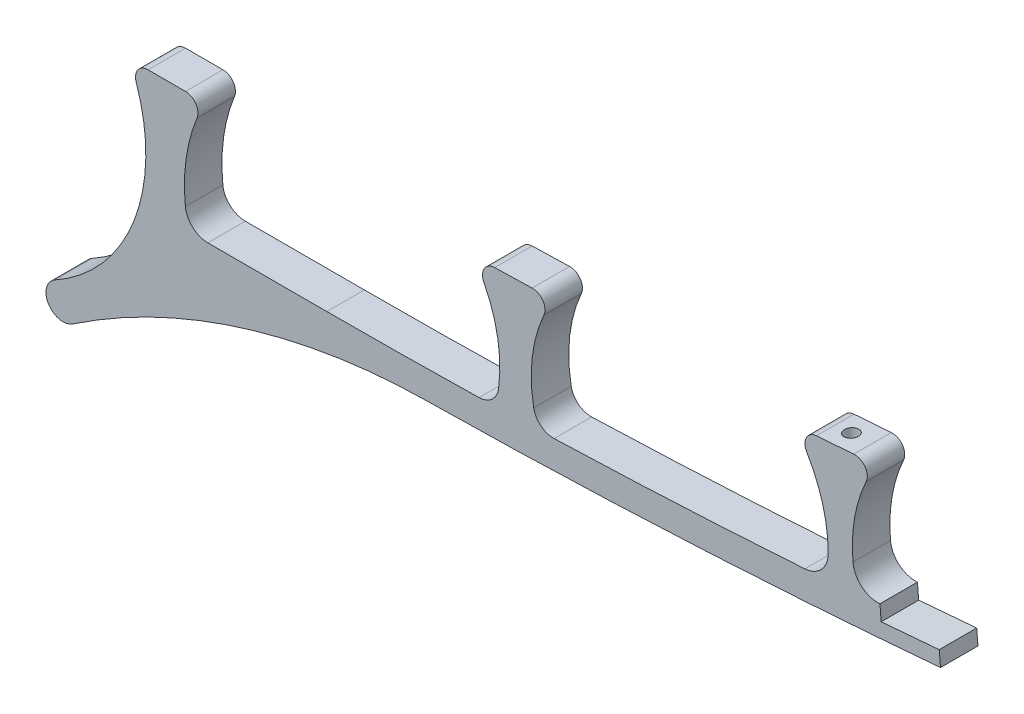
SolidWorks part; units mm, degrees
ref_plane "Front Plane" through (0, 0, 0) normal (0, 0, 1) x (1, 0, 0)
ref_plane "Top Plane" through (0, 0, 0) normal (0, 1, 0) x (1, 0, 0)
ref_plane "Right Plane" through (0, 0, 0) normal (1, 0, 0) x (0, 0, -1)
sketch "Sketch1" plane through (0, 0, 4.0971) normal (0, 0, -1) x (-1, 0, 0)
  line L0 (-62.7619, -51.7222) -> (-58.001, -51.5972) construction
  line L1 (-62.7619, -51.7222) -> (-58.001, -51.5972)
  line L2 (-250.1152, -63.0874) -> (-250.684, -56.8905) construction
  line L3 (-250.1152, -63.0874) -> (-250.684, -56.8905)
  line L4 (5.0134, -50.6875) -> (4.8506, -13.0704)
  line L5 (293.8258, -32.3629) -> (292.5411, -55.9947)
  line L6 (459.2981, -30.7507) -> (468.8231, -30.7507)
  line L7 (423.3798, -61.2307) -> (453.91, -61.2307)
  line L10 (423.2417, -37.1007) -> (607.4086, -37.1007) construction
  line L11 (270.0646, -24.076) -> (423.3798, -30.7507) construction
  line L12 (269.6518, -30.414) -> (423.1036, -37.0947) construction
  line L13 (270.0646, -24.076) -> (423.3798, -30.7507) construction
  line L14 (269.6518, -30.414) -> (423.2417, -37.1007) construction
  line L15 (270.0646, -24.076) -> (423.3798, -30.7507) construction
  line L16 (268.1133, -54.0366) -> (422.0742, -60.7394) construction
  line L17 (268.1133, -54.0366) -> (282.8559, -55.2703)
  line L39 (464.0606, -30.7507) -> (464.0606, -61.2307)
  line L43 (423.3798, -61.2307) -> (607.4086, -61.2307) construction
  line L44 (375.9837, -30.118) -> (375.1663, -60.587)
  line L45 (423.3798, -30.7507) -> (607.4086, -30.7507) construction
  arc A10 (295.9963, -50.7756) -> (301.9161, -57.1188) centre (302.3463, -50.7834) ccw
  arc A11 (301.4662, -31.1688) -> (298.9719, -26.3615) centre (298.7477, -29.5285) ccw
  arc A12 (289.4896, -25.6646) -> (286.3657, -30.1613) centre (289.2483, -28.8304) ccw
  arc A13 (282.8559, -55.2703) -> (289.7096, -49.5155) centre (283.3855, -48.9424) ccw
  arc A17 (301.4662, -31.1688) -> (295.9963, -50.7756) centre (334.0387, -50.8222) ccw
  arc A18 (289.7096, -49.5155) -> (286.3657, -30.1613) centre (251.8722, -46.0867) ccw
  circle A19 centre (490.3927, -92.6507) radius 4.3495
  arc A24 (383.4811, -34.8689) -> (379.749, -56.3925) centre (415.8403, -51.5652) ccw
  circle A29 centre (384.8064, -55.7161) radius 5.1024
  arc A30 (471.8244, -34.9614) -> (468.8231, -30.7507) centre (468.8231, -33.9257) ccw
  arc A31 (459.2981, -30.7507) -> (456.3562, -35.1198) centre (459.2981, -33.9257) ccw
  circle A32 centre (453.6208, -55.4881) radius 5.7427
  arc A33 (383.4811, -34.8689) -> (380.7361, -30.239) centre (380.6595, -33.4131) ccw
  arc A36 (459.3328, -56.0812) -> (456.3562, -35.1198) centre (415.8403, -51.5652) ccw
  arc A39 (368.2424, -34.4601) -> (371.2316, -29.9841) centre (371.1379, -33.1577) cw
  arc A40 (368.2424, -34.4601) -> (370.815, -56.1528) centre (335.0345, -49.3973) cw
  circle A41 centre (365.8012, -55.2062) radius 5.1024
  arc A42 (487.9615, -96.2573) -> (398.3517, -68.1968) centre (396.0818, -232.558) ccw
  arc A43 (471.8244, -34.9614) -> (492.4999, -88.8458) centre (514.2362, -49.5967) ccw
  spline S20 degree 1 poles (365398.7093, 9550.0677) (-365528.5829, -9653.6266) knots -76761.79708 -76761.79708 76766.710756 76766.710756 only from (-53.2401, -51.4722) to (-58.001, -51.5972) construction
  spline S21 degree 1 poles (-53.2401, -51.4722) (-58.001, -51.5972) knots 0 0 1 1
  spline S22 degree 3 poles (-365285.4315, -17668.8025) (-121868.5497, -5930.4401) (121639.8359, 5823.1929) (365056.7131, 17561.5545) knots -76767.936822 -76767.936822 -76767.936822 -76767.936822 76772.733508 76772.733508 76772.733508 76772.733508 only from (-125.7663, -54.1741) to (-121.0093, -53.9446) construction
  spline S23 degree 1 poles (365037.0811, 17563.3216) (-365292.96, -17671.8796) knots -76761.79708 -76761.79708 76766.710756 76766.710756 only from (-116.2524, -53.7151) to (-121.0093, -53.9446) construction
  spline S24 degree 3 poles (-125.7663, -54.1741) (-124.1807, -54.0976) (-122.595, -54.0211) (-121.0093, -53.9446) knots 0 0 0 0 1 1 1 1
  spline S25 degree 1 poles (-116.2524, -53.7151) (-121.0093, -53.9446) knots 0 0 1 1
  spline S26 degree 3 poles (-364867.1723, -25708.7927) (-121740.435, -8582.2589) (121386.2538, 8467.8747) (364512.9914, 25594.4127) knots -76761.79708 -76761.79708 -76761.79708 -76761.79708 76766.710756 76766.710756 76766.710756 76766.710756 only from (-188.7625, -58.0119) to (-184.0117, -57.678) construction
  spline S27 degree 1 poles (364499.1369, 25574.3377) (-364881.0025, -25690.6666) knots -76761.79708 -76761.79708 76766.710756 76766.710756 only from (-179.2609, -57.3441) to (-184.0117, -57.678) construction
  spline S28 degree 3 poles (-188.7625, -58.0119) (-187.1789, -57.9006) (-185.5953, -57.7893) (-184.0117, -57.678) knots 0 0 0 0 1 1 1 1
  spline S29 degree 1 poles (-179.2609, -57.3441) (-184.0117, -57.678) knots 0 0 1 1
  spline S30 degree 3 poles (-364305.982, -33474.3933) (-121635.3274, -11204.5949) (121157.2277, 11080.4514) (363827.8766, 33350.2492) knots -76769.871158 -76769.871158 -76769.871158 -76769.871158 76774.537277 76774.537277 76774.537277 76774.537277 only from (-250.1152, -63.0874) to (-245.3727, -62.6521) construction
  spline S31 degree 1 poles (363807.4185, 33349.3866) (-364311.9821, -33475.959) knots -76761.79708 -76761.79708 76766.710756 76766.710756 only from (-240.6301, -62.2168) to (-245.3727, -62.6521) construction
  spline S32 degree 3 poles (-250.1152, -63.0874) (-248.5344, -62.9423) (-246.9535, -62.7972) (-245.3727, -62.6521) knots 0 0 0 0 1 1 1 1
  spline S33 degree 1 poles (-240.6301, -62.2168) (-245.3727, -62.6521) knots 0 0 1 1
  spline S34 degree 3 poles (-350128.8904, 74318.7235) (10485.7487, 34558.1951) (5966.5817, 298.6907) (-6638.7837, -362.7031) (-14717.7957, 33230.7694) (339737.2718, 110464.3572) knots -40.372141 -40.372141 -40.372141 -40.372141 0.498012 0.498012 41.365106 41.365106 41.365106 41.365106 only from (-260.2582, -26.3703) to (-413.5099, -34.3711) construction
  spline S35 degree 3 poles (-260.2582, -26.3703) (-285.573, -28.8027) (-310.9405, -30.6861) (-362.0399, -33.3672) (-387.7725, -34.1516) (-413.5099, -34.3711) knots 0.333333 0.333333 0.333333 0.333333 0.498012 0.498012 0.664679 0.664679 0.664679 0.664679
  spline S36 degree 3 poles (349486.6475, 77297.8492) (-10774.353, 34462.8749) (-5959.0368, 247.093) (6651.6056, -305.2332) (14440.0911, 33360.4954) (-340666.9575, 107568.7182) knots -40.368098 -40.368098 -40.368098 -40.368098 0.5 0.5 41.36933 41.36933 41.36933 41.36933 only from (270.0646, -24.076) to (423.3798, -30.7507) construction
  spline S37 degree 3 poles (270.0646, -24.076) (295.3995, -26.2893) (320.7823, -27.9531) (371.903, -30.1921) (397.6415, -30.7539) (423.3798, -30.7507) knots 0.335321 0.335321 0.335321 0.335321 0.5 0.5 0.666667 0.666667 0.666667 0.666667
  spline S38 degree 3 poles (34138.9621, 362358.8922) (5323.4883, -4754.5531) (2933.9516, -226.1752) (225.9514, -20.5338) (214.915, -19.7614) (181.7932, -17.6233) (159.6926, -16.4536) (115.476, -14.6188) (93.3552, -13.9534) (60.1689, -13.3398) (49.1062, -13.195) (-2718.3229, 6.5786) (-5521.3328, -4442.3649) (-4432.215, 363984.6204) knots -30.434262 -30.434262 -30.434262 -30.434262 0.125 0.125 0.25 0.25 0.5 0.5 0.75 0.75 0.875 0.875 32.017836 32.017836 32.017836 32.017836 only from (270.0646, -24.076) to (4.8506, -13.0704) construction
  spline S39 degree 3 poles (-37196.4162, 362061.8644) (-5273.4492, -4800.617) (-2922.3434, -251.5149) (-216.1773, -22.4465) (-205.1481, -21.5787) (-172.0462, -19.1541) (-149.9564, -17.7933) (-105.7573, -15.5759) (-83.6432, -14.7191) (-50.4634, -13.8184) (-39.4023, -13.5779) (2727.687, 30.1389) (5568.601, -4394.1839) (1326.2584, 363995.0642) knots -30.434851 -30.434851 -30.434851 -30.434851 0.125 0.125 0.25 0.25 0.5 0.5 0.75 0.75 0.875 0.875 32.017058 32.017058 32.017058 32.017058 only from (-260.2582, -26.3703) to (4.8506, -13.0704) construction
  spline S40 degree 3 poles (270.0646, -24.076) (259.0414, -23.1193) (248.0148, -22.2092) (225.9514, -20.5338) (214.915, -19.7614) (181.7932, -17.6233) (159.6926, -16.4536) (115.476, -14.6188) (93.3552, -13.9534) (60.1689, -13.3398) (49.1062, -13.195) (26.9794, -13.0369) (15.9153, -13.0299) (4.8506, -13.0704) knots 0 0 0 0 0.125 0.125 0.25 0.25 0.5 0.5 0.75 0.75 0.875 0.875 1 1 1 1
  spline S41 degree 3 poles (-260.2582, -26.3703) (-249.2437, -25.3183) (-238.2254, -24.3128) (-216.1773, -22.4465) (-205.1481, -21.5787) (-172.0462, -19.1541) (-149.9564, -17.7933) (-105.7573, -15.5759) (-83.6432, -14.7191) (-50.4634, -13.8184) (-39.4023, -13.5779) (-17.2777, -13.2284) (-6.214, -13.1256) (4.8506, -13.0704) knots 0 0 0 0 0.125 0.125 0.25 0.25 0.5 0.5 0.75 0.75 0.875 0.875 1 1 1 1
  spline S42 degree 1 poles (266.8016, -61.5516) (423.3844, -68.3681) knots 0 0 1 1 construction
  spline S43 degree 1 poles (266.8016, -61.5516) (5.0134, -50.6875) knots 0 0 1 1 construction
  spline S44 degree 1 poles (-256.671, -63.8163) (5.0134, -50.6875) knots 0 0 1 1 construction
  spline S45 degree 1 poles (-256.671, -63.8163) (-413.1891, -71.9871) knots 0 0 1 1 construction
  spline S46 degree 3 poles (423.3844, -68.3681) (417.128, -68.3689) (406.6951, -68.3157) (354.4413, -67.5941) (308.4593, -65.1906) (266.8016, -61.5516) knots 0.335344 0.335344 0.335344 0.335344 0.375021 0.401473 0.666667 0.666667 0.666667 0.666667
  spline S47 degree 3 poles (266.8016, -61.5516) (261.3509, -61.0786) (250.4335, -60.154) (228.7012, -58.4345) (190.549, -55.7631) (136.0425, -52.8693) (81.4825, -51.2368) (43.241, -50.7379) (21.4384, -50.6506) (10.4839, -50.6675) (5.0134, -50.6875) knots 0.00004 0.00004 0.00004 0.00004 0.062532 0.125024 0.250007 0.499973 0.749939 0.874922 0.937414 0.999905 0.999905 0.999905 0.999905
  spline S48 degree 3 poles (5.0134, -50.6875) (-0.4572, -50.7148) (-11.4114, -50.7928) (-33.2124, -51.0686) (-71.4483, -51.8985) (-125.9921, -54.0029) (-180.4716, -57.3683) (-218.5991, -60.3696) (-240.3157, -62.2771) (-251.2247, -63.2961) (-256.671, -63.8163) knots 0.00004 0.00004 0.00004 0.00004 0.062532 0.125023 0.250007 0.499973 0.749939 0.874922 0.937414 0.999905 0.999905 0.999905 0.999905
  spline S49 degree 3 poles (-256.671, -63.8163) (-308.6753, -68.8128) (-360.9473, -71.5416) (-413.1891, -71.9871) knots 0.333356 0.333356 0.333356 0.333356 0.664679 0.664679 0.664679 0.664679
  spline S50 degree 1 poles (267.412, -54.4403) (423.3798, -61.2307) knots 0 0 1 1 construction
  spline S51 degree 1 poles (268.1133, -54.0366) (4.9805, -43.0872) knots 0 0 1 1 construction
  spline S52 degree 1 poles (-257.3958, -56.2506) (4.9805, -43.0872) knots 0 0 1 1 construction
  spline S53 degree 1 poles (-257.3958, -56.2506) (-413.254, -64.3871) knots 0 0 1 1 construction
  spline S54 degree 3 poles (267.412, -54.4403) (276.0285, -55.1931) (290.4062, -56.3442) (313.5674, -57.917) (336.8899, -59.2149) (356.0529, -59.9983) (367.2252, -60.3576) (370.4015, -60.4534) (373.5779, -60.5449) (376.7545, -60.6301) (379.9313, -60.709) (383.1082, -60.7837) (397.5889, -61.095) (411.2827, -61.2322) (423.3798, -61.2307) knots 0.335321 0.335321 0.335321 0.335321 0.390393 0.427108 0.483088 0.539068 0.549181 0.554238 0.559295 0.569408 0.574465 0.579521 0.589635 0.666659 0.666659 0.666659 0.666659 only from (301.9161, -57.1188) to (423.3798, -61.2307)
  spline S55 degree 3 poles (268.1133, -54.0366) (262.6347, -53.5611) (251.6633, -52.6287) (229.8118, -50.8954) (191.4718, -48.2039) (136.6796, -45.2869) (81.8357, -43.6415) (43.4028, -43.1385) (21.4808, -43.0503) (10.477, -43.0671) (4.9805, -43.0872) knots -0.002434 -0.002434 -0.002434 -0.002434 0.060213 0.122861 0.248155 0.498745 0.749335 0.87463 0.937277 0.999924 0.999924 0.999924 0.999924
  spline S56 degree 3 poles (4.9805, -43.0872) (-0.5025, -43.1146) (-11.479, -43.1927) (-33.3456, -43.4694) (-71.6781, -44.3013) (-126.3714, -46.4114) (-181.0006, -49.7861) (-219.224, -52.795) (-241.0064, -54.7082) (-251.9372, -55.7293) (-257.3958, -56.2506) knots 0.000032 0.000032 0.000032 0.000032 0.062525 0.125019 0.250005 0.499978 0.749951 0.874938 0.937431 0.999924 0.999924 0.999924 0.999924
  spline S57 degree 3 poles (-257.3958, -56.2506) (-309.1808, -61.2261) (-361.2324, -63.9435) (-413.254, -64.3871) knots 0.333351 0.333351 0.333351 0.333351 0.664679 0.664679 0.664679 0.664679
  spline S59 degree 3 poles (-413.1844, -71.9874) (-456.1014, -80.1224) (-434.4954, -79.3287) (-479.9907, -101.3371) (-478.4868, -100.9323) knots 0 0 0 0 0.938514 1 1 1 1
  spline S61 degree 1 poles (269.6518, -30.414) (4.8739, -19.4204) knots 0 0 1 1 construction
  spline S63 degree 3 poles (4.8739, -19.4204) (26.9656, -19.3394) (71.1539, -19.6344) (137.3995, -21.6337) (203.5831, -25.1323) (247.6429, -28.5039) (269.6518, -30.414) knots -0.000515 -0.000515 -0.000515 -0.000515 0.249614 0.499743 0.749871 1 1 1 1
  spline S66 degree 1 poles (269.6518, -30.414) (4.8739, -19.4204) knots 0 0 1 1 construction
  spline S68 degree 3 poles (4.8739, -19.4204) (26.9656, -19.3394) (71.1539, -19.6344) (137.3995, -21.6337) (203.5831, -25.1323) (247.6429, -28.5039) (269.6518, -30.414) knots -0.000515 -0.000515 -0.000515 -0.000515 0.249614 0.499743 0.749871 1 1 1 1
  point P81 (310.3019, -33.4897)
  dimension "D3" = 30.48
  dimension "D5" = 6.35
  dimension "D8" = 4.7625
  dimension "D9" = 3.175
  dimension "D10" = 9.525
  dimension "D11" = 12.7
  dimension "D12" = 19.05
  dimension "D16" = 12.7
  dimension "D17" = 3.175
  dimension "D18" = 4.7625
  dimension "D19" = 4.7625
  dimension "D13" = 9.525
  dimension "D14" = 4.7625
  dimension "D15" = 25.4
  dimension "D1" = 37.6174
  dimension "D7" = 6.35
  dimension "D22" = 6.35
extrude "Boss-Extrude5" add sketch "Sketch1" along normal blind 4.7625 and the other way blind 4.7625 contours L7 S54 A10 A17 A11 S37 A12 A18 A13 L17 S55 | A19 | A19 | S54 L44 S37 | L44 S54 A29 A24 A33 S37 region at (-287.273, -56.7987, 4.0971) region at (-490.3927, -92.6507, 4.0971) region at (-372.7453, -43.9651, 4.0971) region at (-378.475, -44.1188, 4.0971)
ref_plane "Plane1" through (0.3209, -4.3662, 0) normal (-0.0733, 0.9973, 0) x (0.9973, 0.0733, 0)
sketch "Sketch6" plane through (0.3209, -4.3662, 0) normal (-0.0733, 0.9973, 0) x (0.9973, 0.0733, 0)
  line L4 (-290.592, -8.8596) -> (-290.592, 0.6654)
  line L10 (-300.0999, 0.6654) -> (-300.0999, -8.8596)
  line L24 (-290.592, -8.8596) -> (-290.592, 0.6654)
  line L27 (-290.592, 0.6654) -> (-300.0999, 0.6654)
  line L29 (-290.592, 0.6654) -> (-300.0999, 0.6654)
  line L30 (-300.0999, -8.8596) -> (-290.592, -8.8596)
  line L31 (-300.0999, -8.8596) -> (-290.592, -8.8596)
  line L34 (-300.0999, 0.6654) -> (-300.0999, -8.8596)
  circle A0 centre (-295.9801, -4.0971) radius 1.778
  dimension "D1" = 0
extrude "Cut-Extrude3" cut sketch "Sketch6" against normal through all contours A0
ref_axis "Axis1" through (-292.1133, -63.4785, 4.0971) along (-0.0733, 0.9973, 0)
ref_plane "Plane2" through (3.0659, -41.7188, 0) normal (-0.0733, 0.9973, 0) x (-0.9947, -0.0731, 0.0729)
sketch "Sketch7" plane through (3.0659, -41.7188, 0) normal (-0.0733, 0.9973, 0) x (-0.9947, -0.0731, 0.0729)
  circle A0 centre (295.4907, -17.5004) radius 1.778 construction
  circle A1 centre (295.4907, -17.5004) radius 1.778
  circle A2 centre (295.4907, -17.5004) radius 3.048
extrude "Cut-Extrude4" cut sketch "Sketch7" along normal blind 3.556 and the other way through all
mirror "Mirror4" about plane through (-4.794, 0.0207, 8.8596) normal (-1, 0.0043, 0) of "Cut-Extrude4", "Cut-Extrude3", "Boss-Extrude5"
sketch "Sketch8" plane through (0, 0, -0.6654) normal (0, 0, -1) x (-1, 0, 0)
  line L0 (-4352.3873, -105.2388) -> (-4674.1378, -106.5977)
  line L1 (-4352.3873, -105.2388) -> (-4352.7091, -29.0388)
  line L2 (-4674.1378, -106.5977) -> (-4674.4596, -30.3977)
  line L3 (-4352.7091, -29.0388) -> (-4674.4596, -30.3977)
  dimension "D1" = 76.2
  dimension "D2" = 321.7505
sketch "Sketch9" plane through (0, 0, -0.6654) normal (0, 0, -1) x (-1, 0, 0)
  line L0 (268.1133, -54.0366) -> (282.8559, -55.2703) construction
  line L1 (268.1133, -54.0366) -> (282.8559, -55.2703)
  line L2 (267.7955, -57.8333) -> (282.5382, -59.067)
  line L3 (282.5382, -59.067) -> (282.8559, -55.2703)
  line L4 (267.7955, -57.8333) -> (267.4671, -61.6096)
  line L5 (268.1133, -54.0366) -> (271.2267, -16.8305)
  line L6 (271.2267, -16.8305) -> (-501.7302, -16.8305)
  line L7 (-501.7302, -16.8305) -> (-501.7302, -147.1798)
  line L8 (-501.7302, -147.1798) -> (267.4671, -61.6096)
  spline S0 degree 3 poles (3301.0551, 674.5447) (1537.391, 185.1791) (-3.796, -521.7342) (-1529.1992, 741.5989) (-741.8929, 2207.0363) knots -3.222654 -3.222654 -3.222654 -3.222654 0.401473 6.512481 6.512481 6.512481 6.512481 only from (398.3517, -68.1968) to (266.8016, -61.5516) construction
  spline S1 degree 3 poles (398.3517, -68.1968) (396.2658, -68.168) (352.3561, -67.4851) (308.4593, -65.1906) (266.8016, -61.5516) knots 0.388247 0.388247 0.388247 0.388247 0.401473 0.666667 0.666667 0.666667 0.666667
  dimension "D1" = 3.81
extrude "Cut-Extrude5" cut sketch "Sketch9" against normal through all contours L7 L8 L4 L2 L3 L1 L5 L6 region at (178.8306, -64.0501, -0.6654)
